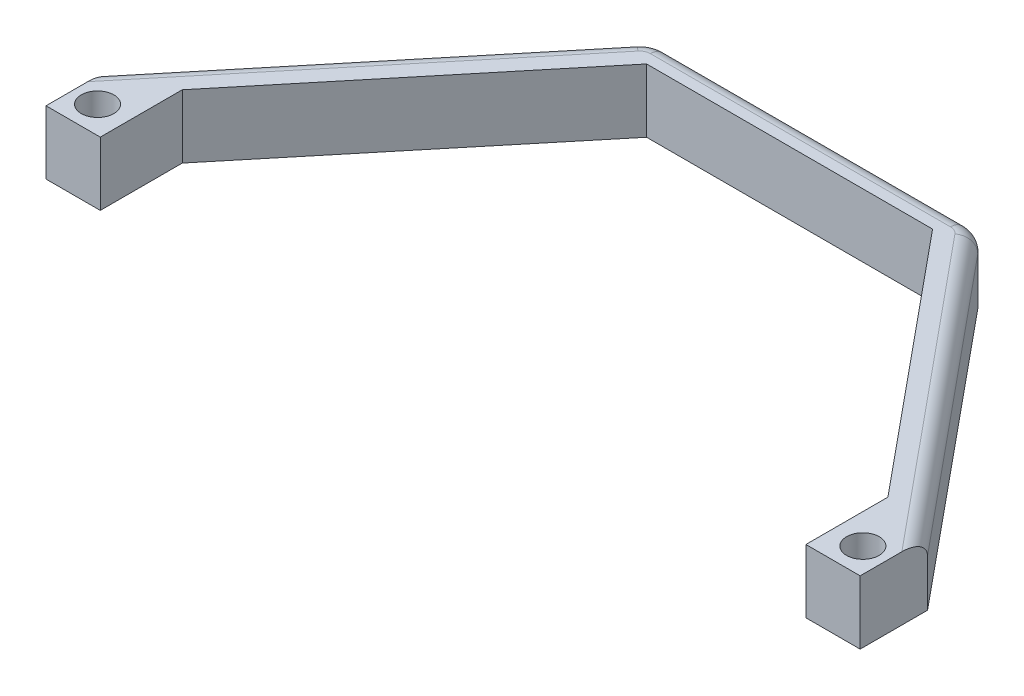
SolidWorks part; units mm, degrees
ref_plane "Front Plane" through (0, 0, 0) normal (0, 0, 1) x (1, 0, 0)
ref_plane "Top Plane" through (0, 0, 0) normal (0, 1, 0) x (1, 0, 0)
ref_plane "Right Plane" through (0, 0, 0) normal (1, 0, 0) x (0, 0, -1)
sketch "Sketch1" plane through (0, 0, 0) normal (0, 1, 0) x (1, 0, 0)
  line L0 (-22.5, 37) -> (22.5, 37)
  line L2 (-22.5, 37) -> (-53, 0)
  line L3 (-53, 0) -> (-75, 0)
  line L4 (-75, 12.4098) -> (-30, 67)
  line L5 (-30, 67) -> (30, 67)
  line L6 (30, 67) -> (75, 12.4098)
  line L7 (75, 0) -> (53, 0)
  line L8 (53, 0) -> (22.5, 37)
  line L16 (-75, 12.4098) -> (-75, 0)
  line L17 (75, 12.4098) -> (75, 0)
  line L18 (-70.5, 5) -> (70.5, 5) construction
  circle A0 centre (70.5, 5) radius 1.65
  circle A1 centre (-70.5, 5) radius 1.65
  point P0 (0, 37)
  point P1 (0, 0)
  point P2 (75, -29.8133)
  point P6 (0, 0)
  point P8 (0, 0)
  point P11 (53, -27.3072)
  point P13 (75, -6.1191)
  point P14 (-53, 3.4496)
  point P15 (0, 67)
  point P22 (0, 5)
  dimension "D8" = 3.3
  dimension "D1" = 45
  dimension "D2" = 30
  dimension "D3" = 67
  dimension "D4" = 60
  dimension "D5" = 106
  dimension "D9" = 141
  dimension "D10" = 5
  dimension "1" = 150
extrude "Boss-Extrude1" add sketch "Sketch1" along normal blind 11.7 contours L5 region at (-39.0177, 0, -19.545)
sketch "Sketch2" plane through (0, 0, 0) normal (0, 1, 0) x (1, 0, 0)
  line L0 (-65, 0) -> (-65, 15.1081)
  line L1 (-53, 0) -> (-75, 0) construction
  line L2 (-65, 15.1081) -> (-26.3459, 62)
  line L3 (-26.3459, 62) -> (26.3459, 62)
  line L4 (0, 0) -> (0, 86.69) construction
  line L5 (-30, 67) -> (30, 67) construction
  line L6 (-75, 12.4098) -> (-30, 67) construction
  line L7 (-75, 12.4098) -> (-75, 0) construction
  line L8 (-65, 0) -> (-53, 0)
  line L9 (-53, 0) -> (-22.5, 37)
  line L10 (-22.5, 37) -> (22.5, 37)
  line L11 (-22.5, 37) -> (22.5, 37) construction
  line L12 (0, 37) -> (0, 62)
  line L13 (53, 0) -> (22.5, 37)
  line L14 (65, 0) -> (53, 0)
  line L15 (65, 15.1081) -> (26.3459, 62)
  line L16 (65, 0) -> (65, 15.1081)
  dimension "D1" = 5
  dimension "D2" = 6
  dimension "D3" = 10
extrude "Cut-Extrude1" cut sketch "Sketch2" along normal blind 51 and the other way blind 10 contours L10 L12 L3 L2 L0 L8 L9 | L14 L16 L15 L3 L12 L10 L13 region at (-32.3955, 0, -35.0591) region at (32.3955, 0, -35.0591)
fillet "Fillet1" radius 3 3 edges at (-52.5, 11.7, -39.7049) (52.5, 11.7, -39.7049) (0, 11.7, -67)
fillet "Fillet2" radius 5 4 edges at (29.5856, 10.8213, -66.1213) (-29.5856, 10.8213, -66.1213) (-30, 4.35, -67) (30, 4.35, -67)
sketch "Sketch3" plane through (0, 11.7, 0) normal (0, 1, 0) x (1, 0, 0)
  circle A0 centre (-70.5, 5) radius 3
  circle A1 centre (70.5, 5) radius 3
  dimension "D1" = 6
extrude "Cut-Extrude2" cut sketch "Sketch3" against normal offset from surface (5.7 mm away) 6 up to face at (-70.5, 0, -3.35)
